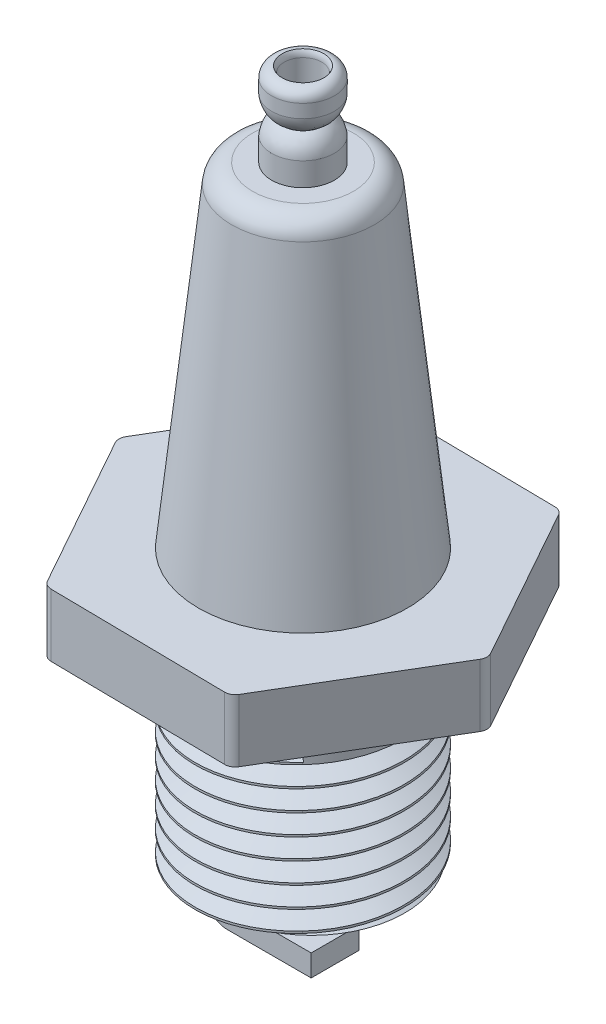
SolidWorks part; units mm, degrees
ref_plane "Front Plane" through (0, 0, 0) normal (0, 0, 1) x (1, 0, 0)
ref_plane "Top Plane" through (0, 0, 0) normal (0, 1, 0) x (1, 0, 0)
ref_plane "Right Plane" through (0, 0, 0) normal (1, 0, 0) x (0, 0, -1)
sketch "Sketch5" plane through (0, 0, 0) normal (0, 1, 0) x (1, 0, 0)
  line L1 (2.1972, -3.931) -> (4.5029, -0.0627)
  line L2 (4.5029, -0.0627) -> (2.3057, 3.8683)
  line L3 (2.3057, 3.8683) -> (-2.1972, 3.931)
  line L4 (-2.1972, 3.931) -> (-4.5029, 0.0627)
  line L5 (-4.5029, 0.0627) -> (-2.3057, -3.8683)
  line L6 (-2.3057, -3.8683) -> (2.1972, -3.931)
  circle A0 centre (0, 0) radius 3.9 construction
  dimension "D1" = 7.8
extrude "Boss-Extrude2" add sketch "Sketch5" along normal blind 1.5
sketch "Sketch6" plane through (0, 0, 0) normal (0, -1, 0) x (1, 0, 0)
  circle A0 centre (0, 0) radius 2.5
  dimension "D1" = 5
extrude "Boss-Extrude3" add sketch "Sketch6" along normal blind 5
sketch "Sketch7" plane through (0, 1.5, 0) normal (0, 1, 0) x (1, 0, 0)
  circle A0 centre (0, 0) radius 2.5
  dimension "D1" = 5
extrude "Boss-Extrude4" add sketch "Sketch7" along normal blind 8 draft 6
fillet "Fillet1" radius 0.5 1 edges at (0, 9.5, 1.6592)
sketch "Sketch8" plane through (0, -5, 0) normal (0, -1, 0) x (1, 0, 0)
  circle A0 centre (0, 0) radius 2.5 construction
  circle A1 centre (0, 0) radius 2.5
curve "Helix/Spiral1" pitch 0.5 height 4 radius 2.5 centre (0, -5, 0) axis (0, 1, 0) start towards (0.7071, 0, 0.7071)
ref_plane "Plane1" through (1.7678, -5, 1.7678) normal (0.7067, 0.0318, -0.7067) x (-0.706, -0.0318, -0.7075)
sketch "Sketch9" plane through (1.7678, -5, 1.7678) normal (0.7067, 0.0318, -0.7067) x (-0.706, -0.0318, -0.7075)
  line L1 (0.3874, 0.0425) -> (-0.0369, 0.2875)
  line L2 (-0.0369, 0.2875) -> (-0.0369, -0.2025)
  line L3 (-0.0369, -0.2025) -> (0.3874, 0.0425)
  circle A0 centre (0.1045, 0.0425) radius 0.1415 construction
  point P1 (0, 0)
  point P7 (0.0663, 0.0425)
  dimension "D1" = 0.49
sweep "Cut-Sweep1" cut profiles "Sketch9" path "Helix/Spiral1" align with end faces yes
sketch "Sketch10" plane through (0, 9.5, 0) normal (0, 1, 0) x (1, 0, 0)
  circle A0 centre (0, 0) radius 0.75
  dimension "D1" = 1.5
extrude "Boss-Extrude5" add sketch "Sketch10" against normal blind 15.5 and the other way blind 2 separate body
sketch "Sketch11" plane through (0, -5, 0) normal (0, -1, 0) x (1, 0, 0)
  line L0 (0, 0) -> (-2.1366, 0) construction
  line L1 (-1.7488, -0.5715) -> (-1.233, -0.5715)
  line L2 (-1.7488, -0.5715) -> (-1.7488, 0.5715)
  line L3 (-1.7488, 0.5715) -> (-1.233, 0.5715)
  line L4 (-1.233, -0.5715) -> (-1.233, 0.5715)
  point P7 (-1.233, 0)
extrude "Boss-Extrude6" add sketch "Sketch11" along normal blind 1.75
sketch "Sketch12" plane through (-1.233, 0, 0) normal (1, 0, 0) x (0, 0, -1)
  line L0 (-0.5715, -6.75) -> (-0.5715, -5) construction
  line L1 (0.5715, -6.75) -> (-0.5715, -6.75)
  line L2 (0.5715, -6.75) -> (0.5715, -6.23)
  line L3 (0.5715, -6.23) -> (-0.5715, -6.23)
  line L4 (-0.5715, -6.75) -> (-0.5715, -6.23)
  dimension "D1" = 0.52
extrude "Boss-Extrude7" add sketch "Sketch12" along normal blind 2
fillet "Fillet2" radius 0.5 2 edges at (-1.7488, -6.75, 0) (-1.233, -6.23, 0)
sketch "Sketch14" plane through (0, 11.5, 0) normal (0, 1, 0) x (1, 0, 0)
  circle A0 centre (0, 0) radius 0.45
  dimension "D1" = 0.9
extrude "Cut-Extrude1" cut sketch "Sketch14" against normal blind 2
fillet "Fillet3" radius 0.25 1 edges at (0, 11.5, 0.75)
fillet "Fillet4" radius 0.25 1 edges at (0, 11.5, 0.45)
sketch "Sketch15" plane through (0, 0, 0) normal (0, 0, 1) x (1, 0, 0)
  line L0 (0, 9.5017) -> (0, 11.4872) construction
  line L1 (0, 10.4945) -> (-0.75, 10.4945) construction
  line L2 (-0.75, 11.25) -> (-0.75, -6) construction
  line L3 (-0.75, 10.0584) -> (-0.75, 10.9305)
  spline S0 degree 2 poles (-0.75, 10.0584) (-0.7192, 10.3448) (-0.488, 10.4945) knots 0 0 0 1 1 1
  spline S1 degree 2 poles (-0.75, 10.9305) (-0.7192, 10.6441) (-0.488, 10.4945) knots 0 0 0 1 1 1
  point P12 (-0.6345, 10.6511)
  point P13 (-0.375, 10.5055)
  point P14 (0, 0)
  point P15 (-0.488, 10.4945)
revolve "Cut-Revolve1" cut sketch "Sketch15" angle 360 about L0
fillet "Fillet5" radius 0.25 6 edges at (2.3057, 0.75, -3.8683) (-2.1972, 0.75, -3.931) (-4.5029, 0.75, -0.0627) (4.5029, 0.75, 0.0627) (-2.3057, 0.75, 3.8683) (2.1972, 0.75, 3.931)
